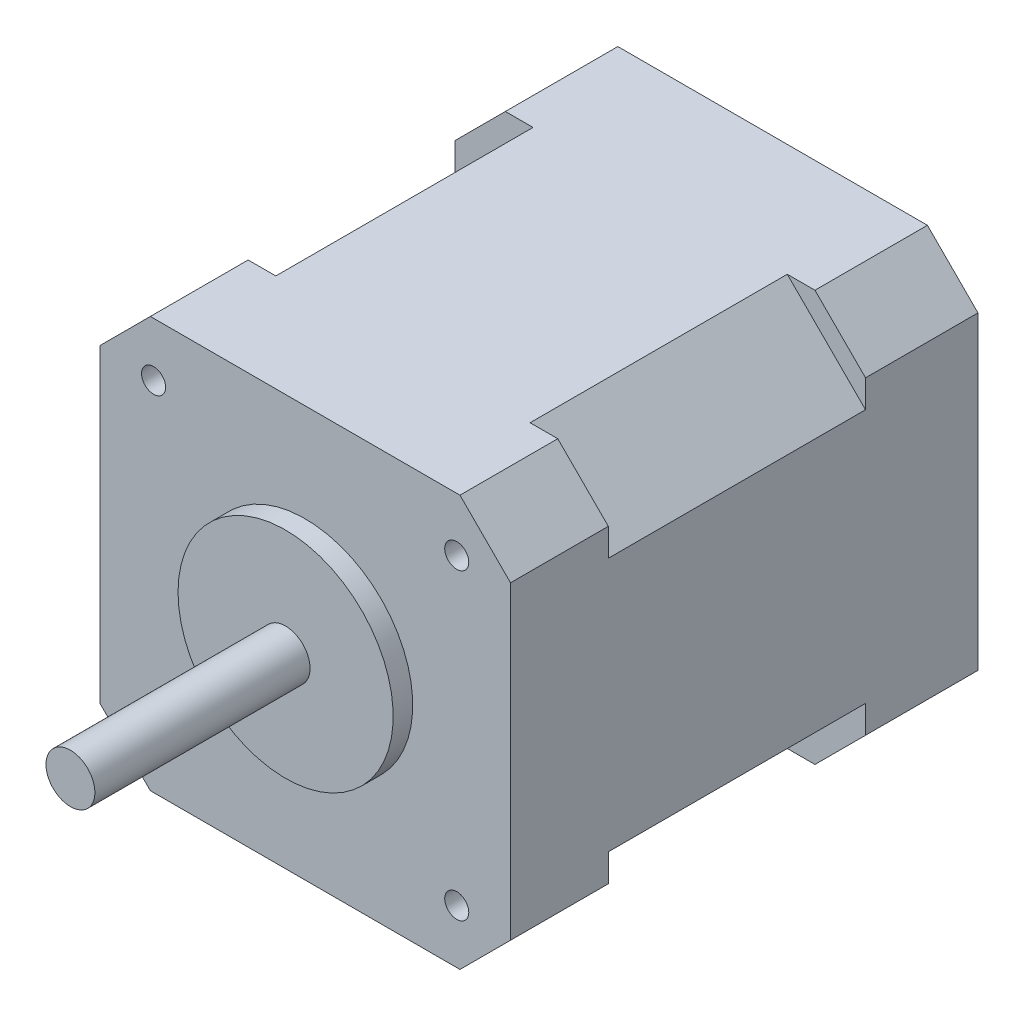
SolidWorks part; units mm, degrees
ref_plane "Front Plane" through (0, 0, 0) normal (0, 0, 1) x (1, 0, 0)
ref_plane "Top Plane" through (0, 0, 0) normal (0, 1, 0) x (1, 0, 0)
ref_plane "Right Plane" through (0, 0, 0) normal (1, 0, 0) x (0, 0, -1)
ref_plane "Plane1" through (0, 0, 0) normal (0, 0, -1) x (-1, 0, 0)
sketch "Sketch1" plane through (0, 0, 0) normal (0, 0, -1) x (-1, 0, 0)
  line L0 (-15.8284, 21) -> (-21, 15.8284)
  line L1 (-21, 15.8284) -> (-21, -15.8284)
  line L2 (-21, -15.8284) -> (-15.8284, -21)
  line L3 (-15.8284, -21) -> (15.8284, -21)
  line L4 (15.8284, -21) -> (21, -15.8284)
  line L5 (21, -15.8284) -> (21, 15.8284)
  line L6 (21, 15.8284) -> (15.8284, 21)
  line L7 (15.8284, 21) -> (-15.8284, 21)
extrude "Boss-Extrude1" add sketch "Sketch1" against normal blind 11.5
sketch "Sketch2" plane through (0, 0, 11.5) normal (0, 0, 1) x (1, 0, 0)
  line L0 (13, -21) -> (-13, -21)
  line L1 (-13, -21) -> (-21, -13)
  line L2 (-21, -13) -> (-21, 13)
  line L3 (-21, 13) -> (-13, 21)
  line L4 (-13, 21) -> (13, 21)
  line L5 (13, 21) -> (21, 13)
  line L6 (21, 13) -> (21, -13)
  line L7 (21, -13) -> (13, -21)
extrude "Boss-Extrude2" add sketch "Sketch2" along normal blind 26.3
sketch "Sketch3" plane through (0, 0, 37.8) normal (0, 0, 1) x (1, 0, 0)
  line L0 (15.8284, 21) -> (21, 15.8284)
  line L1 (21, 15.8284) -> (21, -15.8284)
  line L2 (21, -15.8284) -> (15.8284, -21)
  line L3 (15.8284, -21) -> (-15.8284, -21)
  line L4 (-15.8284, -21) -> (-21, -15.8284)
  line L5 (-21, -15.8284) -> (-21, 15.8284)
  line L6 (-21, 15.8284) -> (-15.8284, 21)
  line L7 (-15.8284, 21) -> (15.8284, 21)
extrude "Boss-Extrude3" add sketch "Sketch3" along normal blind 10
ref_plane "Plane2" through (0, 0, 3.65) normal (0, 0, 1) x (1, 0, 0)
sketch "Sketch4" plane through (0, 0, 3.65) normal (0, 0, 1) x (1, 0, 0)
  line L0 (-31, 1.25) -> (-31, 0.65)
  line L1 (-31, 0.65) -> (-21, 0.65)
  line L2 (-21, 0.65) -> (-21, 1.25)
  line L3 (-21, 1.25) -> (-31, 1.25)
  line L4 (-31, 0.65) -> (-21, 0.65) construction
revolve "Revolve1" add sketch "Sketch4" angle 360 about L4 reverse direction yes
sketch "Sketch5" plane through (0, 0, 3.65) normal (0, 0, 1) x (1, 0, 0)
  line L0 (-31, -0.05) -> (-31, -0.65)
  line L1 (-31, -0.65) -> (-21, -0.65)
  line L2 (-21, -0.65) -> (-21, -0.05)
  line L3 (-21, -0.05) -> (-31, -0.05)
  line L4 (-31, -0.65) -> (-21, -0.65) construction
revolve "Revolve2" add sketch "Sketch5" angle 360 about L4 reverse direction yes
ref_plane "Plane3" through (0, 0, 4.95) normal (0, 0, 1) x (1, 0, 0)
sketch "Sketch6" plane through (0, 0, 4.95) normal (0, 0, 1) x (1, 0, 0)
  line L0 (-31, -0.05) -> (-31, -0.65)
  line L1 (-31, -0.65) -> (-21, -0.65)
  line L2 (-21, -0.65) -> (-21, -0.05)
  line L3 (-21, -0.05) -> (-31, -0.05)
  line L4 (-31, -0.65) -> (-21, -0.65) construction
revolve "Revolve3" add sketch "Sketch6" angle 360 about L4 reverse direction yes
sketch "Sketch7" plane through (0, 0, 4.95) normal (0, 0, 1) x (1, 0, 0)
  line L0 (-31, 1.25) -> (-31, 0.65)
  line L1 (-31, 0.65) -> (-21, 0.65)
  line L2 (-21, 0.65) -> (-21, 1.25)
  line L3 (-21, 1.25) -> (-31, 1.25)
  line L4 (-31, 0.65) -> (-21, 0.65) construction
revolve "Revolve4" add sketch "Sketch7" angle 360 about L4 reverse direction yes
ref_plane "Plane4" through (0, 0, 0) normal (0, -1, 0) x (1, 0, 0)
sketch "Sketch8" plane through (0, 0, 0) normal (0, -1, 0) x (1, 0, 0)
  line L0 (2.5, 71.8) -> (0, 71.8)
  line L1 (0, 71.8) -> (0, 47.8)
  line L2 (0, 47.8) -> (11, 47.8)
  line L3 (11, 47.8) -> (11, 49.8)
  line L4 (11, 49.8) -> (2.5, 49.8)
  line L5 (2.5, 49.8) -> (2.5, 71.8)
  line L6 (0, 71.8) -> (0, 47.8) construction
revolve "Revolve5" add sketch "Sketch8" angle 360 about L6 reverse direction yes
hole_wizard "Hole1" positions "Sketch10" profile "Sketch9" legacy
sketch "Sketch10" plane through (0, 0, 47.8) normal (0, 0, 1) x (1, 0, 0)
  point P0 (-15.5, 15.5)
sketch "Sketch9" plane through (-15.5, 15.5, 47.8) normal (1, 0, 0) x (0, -1, 0)
  line L0 (0, 0) -> (0, 5)
  line L1 (0, 5) -> (1.2295, 5)
  line L2 (1.2295, 5) -> (1.2295, 0)
  line L3 (1.2295, 0) -> (0, 0)
  line L4 (0, 110) -> (0, -10) construction
  dimension "Diameter" = 2.459
  dimension "Depth" = 5
hole_wizard "Hole2" positions "Sketch12" profile "Sketch11" legacy
sketch "Sketch12" plane through (0, 0, 47.8) normal (0, 0, 1) x (1, 0, 0)
  point P0 (-15.5, -15.5)
sketch "Sketch11" plane through (-15.5, -15.5, 47.8) normal (1, 0, 0) x (0, -1, 0)
  line L0 (0, 0) -> (0, 5)
  line L1 (0, 5) -> (1.2295, 5)
  line L2 (1.2295, 5) -> (1.2295, 0)
  line L3 (1.2295, 0) -> (0, 0)
  line L4 (0, 110) -> (0, -10) construction
  dimension "Diameter" = 2.459
  dimension "Depth" = 5
hole_wizard "Hole3" positions "Sketch14" profile "Sketch13" legacy
sketch "Sketch14" plane through (0, 0, 47.8) normal (0, 0, 1) x (1, 0, 0)
  point P0 (15.5, 15.5)
sketch "Sketch13" plane through (15.5, 15.5, 47.8) normal (1, 0, 0) x (0, -1, 0)
  line L0 (0, 0) -> (0, 5)
  line L1 (0, 5) -> (1.2295, 5)
  line L2 (1.2295, 5) -> (1.2295, 0)
  line L3 (1.2295, 0) -> (0, 0)
  line L4 (0, 110) -> (0, -10) construction
  dimension "Diameter" = 2.459
  dimension "Depth" = 5
hole_wizard "Hole4" positions "Sketch16" profile "Sketch15" legacy
sketch "Sketch16" plane through (0, 0, 47.8) normal (0, 0, 1) x (1, 0, 0)
  point P0 (15.5, -15.5)
sketch "Sketch15" plane through (15.5, -15.5, 47.8) normal (1, 0, 0) x (0, -1, 0)
  line L0 (0, 0) -> (0, 5)
  line L1 (0, 5) -> (1.2295, 5)
  line L2 (1.2295, 5) -> (1.2295, 0)
  line L3 (1.2295, 0) -> (0, 0)
  line L4 (0, 110) -> (0, -10) construction
  dimension "Diameter" = 2.459
  dimension "Depth" = 5
ref_axis "Axis1" through (0, 0, 71.8) along (0, 0, -1)
